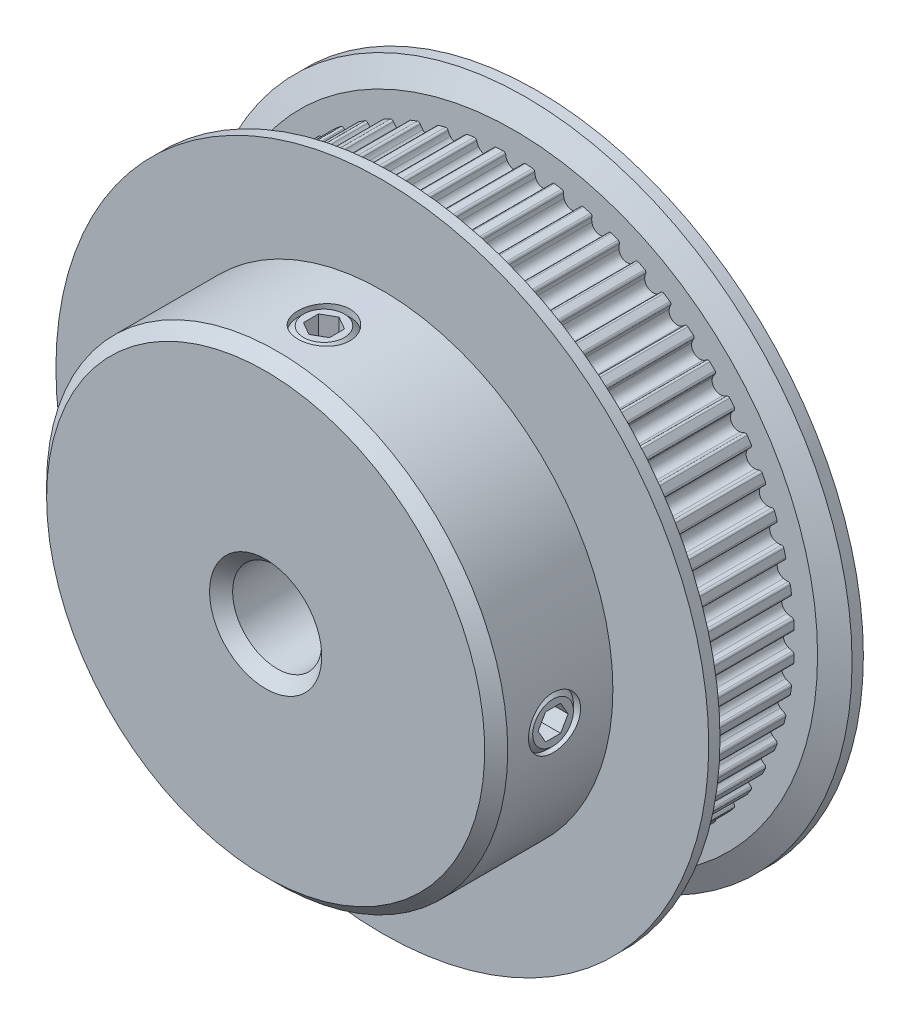
SolidWorks part; units mm, degrees
ref_plane "Front Plane" through (0, 0, 0) normal (0, 0, 1) x (1, 0, 0)
ref_plane "Top Plane" through (0, 0, 0) normal (0, 1, 0) x (1, 0, 0)
ref_plane "Right Plane" through (0, 0, 0) normal (1, 0, 0) x (0, 0, -1)
sketch "Sketch1" plane through (0, 0, 0) normal (0, 0, 1) x (1, 0, 0)
  line L1 (-1.9027, 18.097) -> (1.9027, 18.097) construction
  line L4 (0, 0) -> (0, 18.097) construction
  line L5 (0, 18.097) -> (0, 19.7068) construction
  line L6 (0, 19.101) -> (1.9973, 18.9963) construction
  line L7 (1.9973, 18.9963) -> (2.8966, 18.9017) construction
  line L8 (1.9973, 18.9963) -> (1.9027, 18.097) construction
  line L9 (-1.9973, 18.9963) -> (-1.9027, 18.097) construction
  line L10 (-1.9707, 18.7437) -> (-2.31, 21.971)
  line L11 (-2.31, 21.971) -> (2.31, 21.971)
  line L12 (2.31, 21.971) -> (1.9707, 18.7437)
  circle A0 centre (0, 0) radius 19.101 construction
  circle A1 centre (0, 0) radius 21.971 construction
  circle A2 centre (0, 0) radius 18.847 construction
  arc A3 (-0.4989, 18.4088) -> (0.4989, 18.4088) centre (0, 18.652) ccw
  arc A4 (-0.4989, 18.4088) -> (-0.5897, 18.7039) centre (0.4, 18.847) cw
  arc A5 (-1.9707, 18.7437) -> (-0.7441, 18.8323) centre (0, 0) cw
  arc A6 (-0.5897, 18.7039) -> (-0.7441, 18.8323) centre (-0.7382, 18.6824) ccw
  arc A7 (1.9707, 18.7437) -> (0.7441, 18.8323) centre (0, 0) ccw
  arc A8 (0.5897, 18.7039) -> (0.7441, 18.8323) centre (0.7382, 18.6824) cw
  arc A9 (0.4989, 18.4088) -> (0.5897, 18.7039) centre (-0.4, 18.847) ccw
  point P6 (0, 20.9083)
  point P11 (0, 19.101)
  point P13 (0, 21.971)
  point P14 (0, 18.847)
  dimension "D1" = 1.2015
  dimension "D2" = 0.6058
sketch "Sketch2" plane through (0, 0, 0) normal (1, 0, 0) x (0, 0, -1)
  line L0 (-9.1313, 3) -> (9.1313, 3)
  line L1 (-9.1313, 3) -> (-9.1313, 15.52)
  line L2 (-9.1313, 15.52) -> (-1.2787, 15.52)
  line L3 (-1.2787, 15.52) -> (-1.2787, 21.971)
  line L4 (-1.2787, 21.971) -> (0.2413, 21.971) construction
  line L5 (0.2413, 21.971) -> (0.2413, 18.847) construction
  line L6 (0.2413, 18.847) -> (7.6113, 18.847)
  line L7 (7.6113, 18.847) -> (7.6113, 21.971) construction
  line L8 (7.6113, 21.971) -> (9.1313, 21.971) construction
  line L9 (9.1313, 21.971) -> (9.1313, 3)
  line L10 (-9.1313, 0) -> (9.1313, 0) construction
  line L11 (8.3713, 21.971) -> (7.6113, 20.409)
  line L12 (0.2413, 20.409) -> (-0.5187, 21.971)
  line L13 (-1.2787, 21.971) -> (-0.5187, 21.971)
  line L14 (0.2413, 20.409) -> (0.2413, 18.847)
  line L15 (7.6113, 18.847) -> (7.6113, 20.409)
  line L16 (8.3713, 21.971) -> (9.1313, 21.971)
  arc A0 (0.2413, 20.409) -> (-0.5187, 21.971) centre (-1.7439, 20.409) ccw construction
  arc A1 (7.6113, 20.409) -> (8.3713, 21.971) centre (9.5965, 20.409) cw construction
  point P12 (0.2413, 20.409)
  point P14 (-0.5187, 21.971)
  point P20 (7.6113, 20.409)
  point P21 (8.3713, 21.971)
  point P25 (7.6113, 0)
  point P26 (0.2413, 0)
revolve "Revolve1" add sketch "Sketch2" angle 360 mid plane about L10
sketch "Sketch3" plane through (0, 0, 0) normal (0, 0, 1) x (1, 0, 0)
  line L6 (2.31, 21.971) -> (-2.31, 21.971)
  line L7 (1.9707, 18.7437) -> (2.31, 21.971)
  line L8 (-2.31, 21.971) -> (-1.9707, 18.7437)
  line L9 (2.31, 21.971) -> (-2.31, 21.971)
  line L10 (1.9707, 18.7437) -> (2.31, 21.971)
  line L11 (-2.31, 21.971) -> (-1.9707, 18.7437)
  arc A8 (1.9707, 18.7437) -> (0.7441, 18.8323) centre (0, 0) ccw
  arc A9 (0.7441, 18.8323) -> (0.5897, 18.7039) centre (0.7382, 18.6824) ccw
  arc A10 (0.4989, 18.4088) -> (0.5897, 18.7039) centre (-0.4, 18.847) ccw
  arc A11 (-0.4989, 18.4088) -> (0.4989, 18.4088) centre (0, 18.652) ccw
  arc A12 (-0.5897, 18.7039) -> (-0.4989, 18.4088) centre (0.4, 18.847) ccw
  arc A13 (-0.5897, 18.7039) -> (-0.7441, 18.8323) centre (-0.7382, 18.6824) ccw
  arc A14 (-0.7441, 18.8323) -> (-1.9707, 18.7437) centre (0, 0) ccw
  arc A15 (1.9707, 18.7437) -> (0.7441, 18.8323) centre (0, 0) ccw
  arc A16 (0.7441, 18.8323) -> (0.5897, 18.7039) centre (0.7382, 18.6824) ccw
  arc A17 (0.4989, 18.4088) -> (0.5897, 18.7039) centre (-0.4, 18.847) ccw
  arc A18 (-0.4989, 18.4088) -> (0.4989, 18.4088) centre (0, 18.652) ccw
  arc A19 (-0.5897, 18.7039) -> (-0.4989, 18.4088) centre (0.4, 18.847) ccw
  arc A20 (-0.5897, 18.7039) -> (-0.7441, 18.8323) centre (-0.7382, 18.6824) ccw
  arc A21 (-0.7441, 18.8323) -> (-1.9707, 18.7437) centre (0, 0) ccw
  dimension "D1" = 0
extrude "Cut-Extrude1" cut sketch "Sketch3" against normal up to vertex (7.6113 mm away) from vertex up to point (0, 18.847, -7.6113) starting at point (0, 18.847, -0.2413)
pattern_circular "CirPattern1" count 60 over 360 about axis through (0, 0, 9.1313) along (0, 0, 1) of "Cut-Extrude1"
sketch "Sketch4" plane through (0, 0, 0) normal (1, 0, 0) x (0, -1, 0)
  line L0 (0, -1.2787) -> (0, -9.1313) construction
  line L1 (-15.52, -1.2787) -> (15.52, -1.2787) construction
  line L2 (-15.52, -9.1313) -> (15.52, -9.1313) construction
  circle A0 centre (0, -5.205) radius 1.7526
extrude "Cut-Extrude2" cut sketch "Sketch4" along normal through all
ref_plane "Plane1" through (0, 0, 5.205) normal (0, 0, 1) x (1, 0, 0)
sketch "Sketch5" plane through (0, 0, 5.205) normal (0, 0, 1) x (1, 0, 0)
  line L0 (0, 0.1664) -> (0, 15.52) construction
  line L1 (3, -1.3716) -> (3, 0)
  line L2 (3.381, -1.7526) -> (15.0397, -1.7526)
  line L3 (3, 0) -> (15.52, 0) construction
  line L4 (3, 0) -> (15.4207, 0)
  line L5 (15.4207, 0) -> (15.4207, -1.3716)
  line L6 (3.381, -1.7526) -> (3, -1.3716)
  line L7 (15.4207, -1.3716) -> (15.0397, -1.7526)
  circle A0 centre (0, 0) radius 15.52 construction
  circle A1 centre (0, 0) radius 3 construction
  point P2 (3, -1.7526)
  point P11 (15.4207, -1.7526)
revolve "Revolve2" add sketch "Sketch5" angle 360 mid plane about L4
sketch "Sketch6" plane through (15.4207, 5.3841, 0) normal (-1, 0, 0) x (0, -1, 0)
  line L1 (5.3841, 6.2169) -> (4.5078, 5.7109)
  line L2 (4.5078, 5.7109) -> (4.5078, 4.6991)
  line L3 (4.5078, 4.6991) -> (5.3841, 4.1931)
  line L4 (5.3841, 4.1931) -> (6.2604, 4.6991)
  line L5 (6.2604, 4.6991) -> (6.2604, 5.7109)
  line L6 (6.2604, 5.7109) -> (5.3841, 6.2169)
  circle A0 centre (5.3841, 5.205) radius 0.8763 construction
  dimension "D1" = 1.7526
extrude "Cut-Extrude3" cut sketch "Sketch6" along normal blind 1.3144
pattern_circular "CirPattern2" count 2 over 90 about axis through (0, 0, 9.1313) along (0, 0, 1) of "Cut-Extrude2", "Revolve2", "Cut-Extrude3"
chamfer "Chamfer1" distance 0.776 angle 45 2 edges at (3, 0, 9.1313) (15.52, 0, 9.1313)
ref_axis "Center Axis 1" through (0, 0, -9.1313) along (0, 0, 1)
ref_plane "Contact Plane 1" through (0, 0, 9.1313) normal (0, 0, 1) x (1, 0, 0)
ref_plane "Contact Plane 2" through (0, 0, -9.1313) normal (0, 0, -1) x (-1, 0, 0)
equation "\"D2@Sketch1\" = \"D1@Sketch1\"/2"
equation "\"D1@Sketch6\" = \"Set Screw@Sketch4\" / 2"
equation "\"D1@Cut-Extrude3\" = \"D1@Sketch6\"*.75"
equation "\"D1@Chamfer1\"=\"Hub Dia@Sketch2\"*.025"
